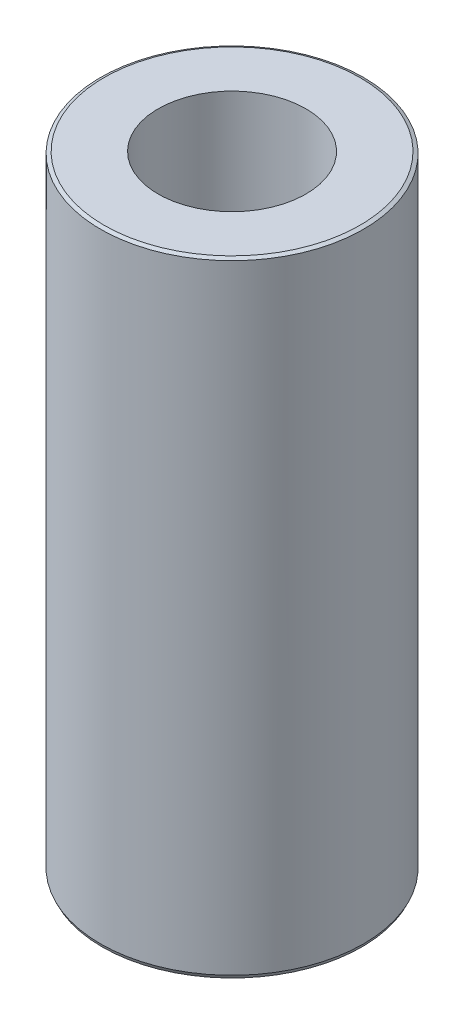
SolidWorks part; units mm, degrees
ref_plane "Front Plane" through (0, 0, 0) normal (0, 0, 1) x (1, 0, 0)
ref_plane "Top Plane" through (0, 0, 0) normal (0, 1, 0) x (1, 0, 0)
ref_plane "Right Plane" through (0, 0, 0) normal (1, 0, 0) x (0, 0, -1)
sketch "Sketch1" plane through (0, 0, 0) normal (0, 1, 0) x (1, 0, 0)
  circle A0 centre (0, 0) radius 50
  dimension "SHAFT_OD" = 100
extrude "Boss-Extrude1" add sketch "Sketch1" along normal blind 237.2496
sketch "Sketch2" plane through (0, 0, 0) normal (0, 1, 0) x (1, 0, 0)
  circle A0 centre (0, 0) radius 28.0944
  dimension "BORE_D" = 56.1888
extrude "Cut-Extrude1" cut sketch "Sketch2" along normal through all
chamfer "Chamfer1" distance 0.6312 angle 64.966 2 edges at (0, 237.2496, 50) (0, 0, 50) first distance on face at (0, 237.2496, 50) first distance on face at (0, 0, 28.0944)
